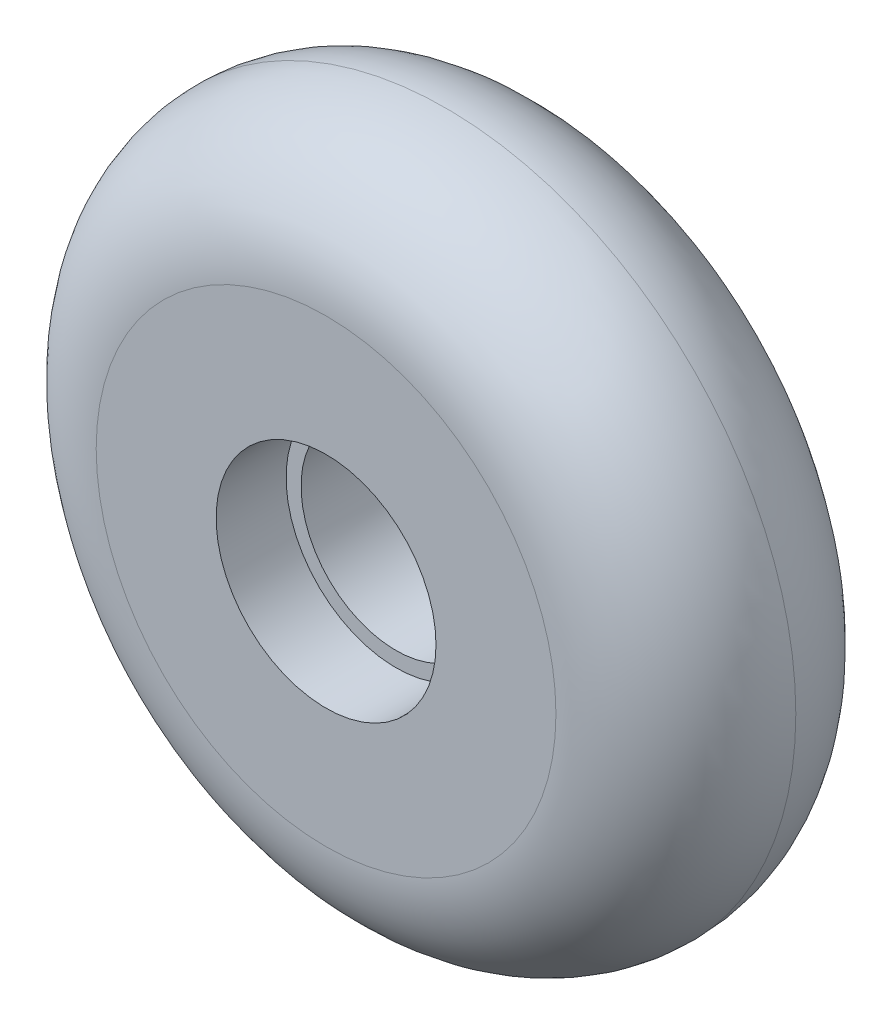
SolidWorks part; units mm, degrees
ref_plane "Face" through (0, 0, 0) normal (0, 0, 1) x (1, 0, 0)
ref_plane "Dessus" through (0, 0, 0) normal (0, 1, 0) x (1, 0, 0)
ref_plane "Droite" through (0, 0, 0) normal (1, 0, 0) x (0, 0, -1)
sketch "Esquisse1" plane through (0, 0, 0) normal (0, 0, 1) x (1, 0, 0)
  circle A0 centre (0, 0) radius 35
  dimension "D1" = 70
extrude "Extrusion1" add sketch "Esquisse1" along normal blind 24
fillet "Congé1" radius 12 1 edges at (35, 0, 24)
fillet "Congé2" radius 12 1 edges at (35, 0, 0)
sketch "Esquisse2" plane through (0, 0, 24) normal (0, 0, 1) x (1, 0, 0)
  circle A0 centre (0, 0) radius 11
  dimension "D1" = 22
extrude "Enlèv. mat.-Extru.1" cut sketch "Esquisse2" against normal blind 7
sketch "Esquisse3" plane through (0, 0, 0) normal (0, 0, -1) x (-1, 0, 0)
  circle A0 centre (0, 0) radius 11
  dimension "D1" = 22
extrude "Enlèv. mat.-Extru.2" cut sketch "Esquisse3" against normal blind 7
sketch "Esquisse5" plane through (0, 0, 17) normal (0, 0, 1) x (1, 0, 0)
  circle A0 centre (0, 0) radius 9.5
  dimension "D1" = 19
extrude "Enlèv. mat.-Extru.3" cut sketch "Esquisse5" against normal through all
sketch "Esquisse6" plane through (0, 0, 17) normal (0, 0, 1) x (1, 0, 0)
  line L0 (0, 0) -> (0, 11) construction
  line L1 (0, 0) -> (9.5263, -5.5) construction
  line L2 (0, 0) -> (-9.5263, -5.5) construction
  circle A0 centre (0, 0) radius 11 construction
  circle A1 centre (0, 0) radius 11 construction
  dimension "D1" = 120
  dimension "D2" = 120
